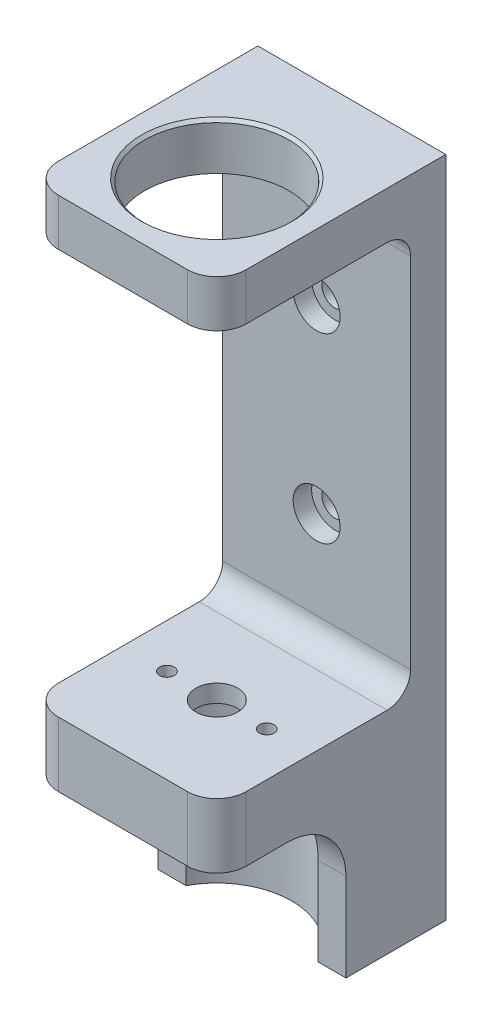
SolidWorks part; units mm, degrees
ref_plane "Alzado" through (0, 0, 0) normal (0, 0, 1) x (1, 0, 0)
ref_plane "Planta" through (0, 0, 0) normal (0, 1, 0) x (1, 0, 0)
ref_plane "Vista lateral" through (0, 0, 0) normal (1, 0, 0) x (0, 0, -1)
ref_plane "Plano1" through (14, 0, 0) normal (1, 0, 0) x (0, 0, -1)
sketch "Croquis1" plane through (14, 0, 0) normal (1, 0, 0) x (0, 0, -1)
  line L0 (-28, 72) -> (-28, 0)
  line L1 (-28, 0) -> (3, 0)
  line L2 (3, 0) -> (3, 72)
  line L3 (3, 72) -> (-28, 72)
extrude "Saliente-Extruir1" add sketch "Croquis1" against normal blind 28
sketch "Croquis2" plane through (-14, 0, 0) normal (-1, 0, 0) x (0, 0, 1)
  line L0 (28, 70) -> (1, 70)
  line L1 (1, 70) -> (1, 1)
  line L2 (1, 1) -> (28, 1)
  line L3 (28, 1) -> (28, 70)
extrude "Cortar-Extruir1" cut sketch "Croquis2" against normal through all
ref_plane "Plano2" through (0, 0, 14) normal (0, 0, -1) x (-1, 0, 0)
sketch "Croquis3" plane through (0, 0, 14) normal (0, 0, -1) x (-1, 0, 0)
  line L0 (-4.2, 72) -> (0, 72)
  line L1 (0, 72) -> (0, 73.5)
  line L2 (0, 73.5) -> (-2.7, 73.5)
  line L3 (0, 72) -> (0, 73.5) construction
  arc A0 (-2.7, 73.5) -> (-4.2, 72) centre (-4.2, 73.5) cw
ref_plane "Plano3" through (0, 0, 14) normal (0, 0, 1) x (1, 0, 0)
sketch "Croquis4" plane through (0, 0, 14) normal (0, 0, 1) x (1, 0, 0)
  line L0 (2.75, 2) -> (0, 2)
  line L1 (0, 2) -> (0, 1)
  line L2 (0, 1) -> (3.75, 1)
  line L3 (0, 2) -> (0, 1) construction
  arc A0 (3.75, 1) -> (2.75, 2) centre (3.75, 2) cw
sketch "Croquis5" plane through (0, 0, 14) normal (0, 0, -1) x (-1, 0, 0)
  line L0 (-13, -10) -> (0, -10)
  line L1 (0, -10) -> (0, 0)
  line L2 (0, 0) -> (-13, 0)
  line L3 (-13, 0) -> (-13, -10)
  line L4 (0, -10) -> (0, 0) construction
revolve "Revolución3" add sketch "Croquis5" angle 360 about L4 reverse direction yes
sketch "Croquis6" plane through (0, 0, 14) normal (0, 0, -1) x (-1, 0, 0)
  line L0 (-12.75, -10) -> (0, -10)
  line L1 (0, -10) -> (0, 2)
  line L2 (0, 2) -> (-2.3, 2)
  line L3 (-2.3, 2) -> (-2.3, 1)
  line L4 (-2.3, 1) -> (-2.25, 1)
  line L5 (-2.25, 1) -> (-2.25, 0)
  line L6 (-2.25, 0) -> (-12.75, 0)
  line L7 (-12.75, 0) -> (-12.75, -10)
  line L8 (0, -10) -> (0, 2) construction
revolve "Cortar-Revolución1" cut sketch "Croquis6" angle 360 about L8 reverse direction yes
hole_wizard "Diámetro de taladro Ø2.5 (2.5)2" positions "Croquis12" profile "Croquis11" hole size "Ø2.5" standard "Ansi Metric"
sketch "Croquis12" plane through (0, 1, 0) normal (0, 1, 0) x (1, 0, 0)
  point P0 (8.5, -14)
  point P1 (-8.5, -14)
sketch "Croquis11" plane through (8.5, 1, 14) normal (1, 0, 0) x (0, 0, 1)
  line L0 (0, 0) -> (0, 11)
  line L1 (0, 11) -> (1.25, 11)
  line L2 (1.25, 11) -> (1.25, 0)
  line L5 (1.25, 0) -> (0, 0)
  line L11 (0, -6.35) -> (0, 107.95) construction
  dimension "Diámetro de taladro hasta el siguiente" = 2.5
  dimension "Profundidad de taladro hasta el siguiente" = 11
fillet "Redondeo3" radius 5 2 edges at (0, 70, 1) (0, 1, 1) tangent propagation no
fillet "Redondeo4" radius 3 4 edges at (-14, 0.5, 28) (14, 71, 28) (14, 0.5, 28) (-14, 71, 28) tangent propagation no
sketch "Croquis14" plane through (0, 0, 0) normal (0, -1, 0) x (1, 0, 0)
  line L4 (11, 28) -> (-11, 28)
  line L5 (-14, 25) -> (-14, -3)
  line L6 (-14, -3) -> (14, -3)
  line L7 (14, -3) -> (14, 25)
  line L8 (11, 28) -> (-11, 28)
  line L9 (-14, 25) -> (-14, -3)
  line L10 (-14, -3) -> (14, -3)
  line L11 (14, -3) -> (14, 25)
  circle A0 centre (0, 14) radius 13 construction
  circle A1 centre (0, 14) radius 13
  arc A2 (-11, 28) -> (-14, 25) centre (-11, 25) ccw
  arc A3 (14, 25) -> (11, 28) centre (11, 25) ccw
  arc A4 (-11, 28) -> (-14, 25) centre (-11, 25) ccw
  arc A5 (14, 25) -> (11, 28) centre (11, 25) ccw
  dimension "D1" = 0
extrude "Saliente-Extruir2" add sketch "Croquis14" along normal blind 10
sketch "Croquis15" plane through (0, 0, -3) normal (0, 0, -1) x (-1, 0, 0)
  line L4 (-14, 72) -> (-14, -10)
  line L5 (-14, -10) -> (14, -10)
  line L6 (14, -10) -> (14, 72)
  line L7 (14, 72) -> (-14, 72)
  line L8 (-14, 72) -> (-14, -10)
  line L9 (-14, -10) -> (14, -10)
  line L10 (14, -10) -> (14, 72)
  line L11 (14, 72) -> (-14, 72)
  dimension "D1" = 0
extrude "Saliente-Extruir3" add sketch "Croquis15" along normal blind 6
sketch "Croquis16" plane through (0, 0, 0) normal (0, -1, 0) x (1, 0, 0)
  line L0 (0, 14) -> (2.7, 14) construction
  circle A0 centre (0, 14) radius 3.55
  dimension "D1" = 7.1
extrude "Cortar-Extruir2" cut sketch "Croquis16" against normal up to surface (72 mm away) up to face at (0, 72, 14.8738)
sketch "Croquis17" plane through (0, 72, 0) normal (0, 1, 0) x (1, 0, 0)
  line L4 (-11, -28) -> (11, -28)
  line L5 (14, -25) -> (14, 9)
  line L6 (14, 9) -> (-14, 9)
  line L7 (-14, 9) -> (-14, -25)
  line L8 (-11, -28) -> (11, -28)
  line L9 (14, -25) -> (14, 9)
  line L10 (14, 9) -> (-14, 9)
  line L11 (-14, 9) -> (-14, -25)
  circle A0 centre (0, -14) radius 3.55 construction
  circle A1 centre (0, -14) radius 3.55
  arc A2 (11, -28) -> (14, -25) centre (11, -25) ccw
  arc A3 (-14, -25) -> (-11, -28) centre (-11, -25) ccw
  arc A4 (11, -28) -> (14, -25) centre (11, -25) ccw
  arc A5 (-14, -25) -> (-11, -28) centre (-11, -25) ccw
  dimension "D1" = 0
extrude "Saliente-Extruir4" add sketch "Croquis17" along normal blind 6
sketch "Croquis18" plane through (-14, 0, 0) normal (-1, 0, 0) x (0, 0, 1)
  line L0 (6, 70) -> (1, 70)
  line L1 (-3, 66) -> (-3, 5)
  line L2 (1, 1) -> (6, 1)
  line L8 (25, 70) -> (25, 78)
  line L9 (25, 78) -> (-9, 78)
  line L10 (-9, 78) -> (-9, -10)
  line L11 (-9, -10) -> (25, -10)
  line L12 (25, -10) -> (25, 1)
  line L13 (25, 1) -> (6, 1)
  line L14 (1, 6) -> (1, 65)
  line L15 (6, 70) -> (25, 70)
  line L16 (25, 70) -> (25, 78)
  line L17 (25, 78) -> (-9, 78)
  line L18 (-9, 78) -> (-9, -10)
  line L19 (-9, -10) -> (25, -10)
  line L20 (25, -10) -> (25, 1)
  line L21 (25, 1) -> (6, 1)
  line L22 (1, 6) -> (1, 65)
  line L23 (6, 70) -> (25, 70)
  arc A0 (-3, 5) -> (1, 1) centre (1, 5) ccw
  arc A1 (1, 70) -> (-3, 66) centre (1, 66) ccw
  arc A2 (1, 6) -> (6, 1) centre (6, 6) ccw
  arc A3 (6, 70) -> (1, 65) centre (6, 65) ccw
  arc A4 (1, 6) -> (6, 1) centre (6, 6) ccw
  arc A5 (6, 70) -> (1, 65) centre (6, 65) ccw
  arc M18 (6, 1) -> (1, 6) centre (6, 6) cw
  line M19 (1, 6) -> (1, 65)
  arc M20 (1, 65) -> (6, 70) centre (6, 65) cw
  dimension "D2" = 4
  dimension "D3" = 4
  dimension "D1" = 0
extrude "Cortar-Extruir3" cut sketch "Croquis18" against normal through all contours L0 A1 L1 A0 L2 M18 M19 M20 region at (-14, 35.5, -0.8533)
sketch "Croquis19" plane through (0, -10, 0) normal (0, -1, 0) x (1, 0, 0)
  line L0 (-14, 8) -> (-11.25, 8)
  line L1 (11.25, 8) -> (14, 8)
  line L4 (11, 28) -> (-11, 28)
  line L5 (-14, 25) -> (-14, -9)
  line L6 (-14, -9) -> (14, -9)
  line L7 (14, -9) -> (14, 25)
  line L8 (11, 28) -> (-11, 28)
  line L9 (-14, 8) -> (-14, -9)
  line L10 (-14, -9) -> (14, -9)
  line L11 (14, -9) -> (14, 8)
  circle A0 centre (0, 14) radius 12.75 construction
  arc A1 (-11.25, 8) -> (11.25, 8) centre (0, 14) ccw
  arc A2 (14, 25) -> (11, 28) centre (11, 25) ccw
  arc A3 (-11, 28) -> (-14, 25) centre (-11, 25) ccw
  arc A4 (14, 25) -> (11, 28) centre (11, 25) ccw
  arc A5 (-11, 28) -> (-14, 25) centre (-11, 25) ccw
  circle M10 centre (0, 14) radius 12.75
  line M14 (-14, 25) -> (-14, -9)
  line M15 (-14, -9) -> (14, -9)
  line M16 (14, -9) -> (14, 25)
  dimension "D2" = 17
  dimension "D1" = 0
extrude "Saliente-Extruir5" add sketch "Croquis19" along normal blind 10 contours L1 L0 M10 M14 M15 M16 region at (0, -10, -2.185)
fillet "Redondeo5" radius 10 2 edges at (12.625, -10, 8) (-12.625, -10, 8)
sketch "Croquis20" plane through (0, 0, -3) normal (0, 0, 1) x (1, 0, 0)
  line L0 (0, 5) -> (0, 66) construction
  line L1 (14, 5) -> (-14, 5) construction
  line L2 (14, 66) -> (-14, 66) construction
  circle A0 centre (0, 51) radius 2.25
  circle A1 centre (0, 20) radius 2.25
  point P6 (0, 20)
  point P7 (0, 51)
  dimension "D3" = 4.5
  dimension "D4" = 4.5
  dimension "D1" = 15
  dimension "D2" = 15
extrude "Cortar-Extruir4" cut sketch "Croquis20" against normal through all
sketch "Croquis21" plane through (0, 0, -3) normal (0, 0, 1) x (1, 0, 0)
  line L4 (-14, 66) -> (-14, 5)
  line L5 (-14, 5) -> (14, 5)
  line L6 (14, 5) -> (14, 66)
  line L7 (14, 66) -> (-14, 66)
  line L8 (-14, 66) -> (-14, 5)
  line L9 (-14, 5) -> (14, 5)
  line L10 (14, 5) -> (14, 66)
  line L11 (14, 66) -> (-14, 66)
  circle A0 centre (0, 20) radius 2.25 construction
  circle A1 centre (0, 20) radius 2.25
  circle A2 centre (0, 51) radius 2.25 construction
  circle A3 centre (0, 51) radius 2.25
  circle A4 centre (0, 51) radius 4
  circle A5 centre (0, 20) radius 4
  circle M6 centre (0, 51) radius 2.25
  circle M7 centre (0, 20) radius 2.25
  dimension "D2" = 8
  dimension "D3" = 8
  dimension "D1" = 0
extrude "Cortar-Extruir5" cut sketch "Croquis21" against normal blind 3.15 contours A4 M6 | A5 M7 region at (-3.8869, 51, -3) region at (-3.8869, 20, -3)
sketch "Croquis22" plane through (0, 0, 0) normal (0, -1, 0) x (1, 0, 0)
  circle A0 centre (8.5, 14) radius 1.25 construction
  circle A1 centre (0, 14) radius 12.75
  circle A2 centre (0, 14) radius 12.75
  circle A3 centre (0, 14) radius 3.55 construction
  circle A4 centre (-8.5, 14) radius 1.25 construction
  circle A5 centre (8.5, 14) radius 1.25
  circle A6 centre (0, 14) radius 3.55
  circle A7 centre (-8.5, 14) radius 1.25
  dimension "D1" = 0
extrude "Saliente-Extruir6" add sketch "Croquis22" along normal blind 2
sketch "Croquis23" plane through (0, 78, 0) normal (0, 1, 0) x (1, 0, 0)
  line L0 (-16, 9) -> (-16, -25)
  line L1 (-11, -30) -> (11, -30)
  line L2 (16, -25) -> (16, 9)
  line L4 (-11, -28) -> (11, -28)
  line L5 (14, -25) -> (14, 9)
  line L6 (14, 9) -> (-14, 9)
  line L7 (-14, 9) -> (-14, -25)
  line L8 (-11, -28) -> (11, -28)
  line L9 (14, -25) -> (14, 9)
  line L10 (14, 9) -> (-14, 9)
  line L11 (-14, 9) -> (-14, -25)
  line L12 (14, 9) -> (16, 9)
  line L13 (-14, 9) -> (-16, 9)
  line L14 (16, -25) -> (16, 11) construction
  line L15 (16, 11) -> (-16, 11) construction
  line L16 (-16, 11) -> (-16, -25) construction
  arc A0 (-16, -25) -> (-11, -30) centre (-11, -25) ccw
  arc A1 (11, -30) -> (16, -25) centre (11, -25) ccw
  arc A2 (-14, -25) -> (-11, -28) centre (-11, -25) ccw
  arc A3 (11, -28) -> (14, -25) centre (11, -25) ccw
  arc A4 (-14, -25) -> (-11, -28) centre (-11, -25) ccw
  arc A5 (11, -28) -> (14, -25) centre (11, -25) ccw
  arc M13 (-14, -25) -> (-11, -28) centre (-11, -25) ccw
  line M14 (-11, -28) -> (11, -28)
  arc M15 (11, -28) -> (14, -25) centre (11, -25) ccw
  line M16 (14, -25) -> (14, 9)
  line M18 (-14, 9) -> (-14, -25)
  dimension "D1" = 0
  dimension "D2" = 2
extrude "Saliente-Extruir7" add sketch "Croquis23" against normal up to surface (8 mm away) contours L1 A1 L2 L12 L13 L0 A0 M16 M15 M14 M13 M18 region at (-15, 78, -8.4955) up to face at (-3.55, 70, 14)
sketch "Croquis24" plane through (-14, 0, 0) normal (-1, 0, 0) x (0, 0, 1)
  line L7 (1, 70) -> (-9, 70)
  line L8 (-9, 70) -> (-9, -20)
  line L9 (-9, -20) -> (8, -20)
  line L10 (18, -10) -> (25, -10)
  line L11 (25, -10) -> (25, 1)
  line L12 (25, 1) -> (1, 1)
  line L13 (-3, 5) -> (-3, 66)
  line L14 (1, 70) -> (-9, 70)
  line L15 (-9, 70) -> (-9, -20)
  line L16 (-9, -20) -> (8, -20)
  line L17 (18, -10) -> (25, -10)
  line L18 (25, -10) -> (25, 1)
  line L19 (25, 1) -> (1, 1)
  line L20 (-3, 5) -> (-3, 66)
  arc A3 (18, -10) -> (8, -20) centre (18, -20) ccw
  arc A4 (-3, 5) -> (1, 1) centre (1, 5) ccw
  arc A5 (1, 70) -> (-3, 66) centre (1, 66) ccw
  arc A6 (18, -10) -> (8, -20) centre (18, -20) ccw
  arc A7 (-3, 5) -> (1, 1) centre (1, 5) ccw
  arc A8 (1, 70) -> (-3, 66) centre (1, 66) ccw
  dimension "D1" = 0
extrude "Saliente-Extruir8" add sketch "Croquis24" along normal blind 2
sketch "Croquis25" plane through (14, 0, 0) normal (1, 0, 0) x (0, 0, -1)
  line L7 (9, -20) -> (9, 70)
  line L8 (9, 70) -> (-1, 70)
  line L9 (3, 66) -> (3, 5)
  line L10 (-1, 1) -> (-25, 1)
  line L11 (-25, 1) -> (-25, -10)
  line L12 (-25, -10) -> (-18, -10)
  line L13 (-8, -20) -> (9, -20)
  line L14 (9, -20) -> (9, 70)
  line L15 (9, 70) -> (-1, 70)
  line L16 (3, 66) -> (3, 5)
  line L17 (-1, 1) -> (-25, 1)
  line L18 (-25, 1) -> (-25, -10)
  line L19 (-25, -10) -> (-18, -10)
  line L20 (-8, -20) -> (9, -20)
  arc A3 (3, 66) -> (-1, 70) centre (-1, 66) ccw
  arc A4 (-1, 1) -> (3, 5) centre (-1, 5) ccw
  arc A5 (-8, -20) -> (-18, -10) centre (-18, -20) ccw
  arc A6 (3, 66) -> (-1, 70) centre (-1, 66) ccw
  arc A7 (-1, 1) -> (3, 5) centre (-1, 5) ccw
  arc A8 (-8, -20) -> (-18, -10) centre (-18, -20) ccw
  dimension "D1" = 0
extrude "Saliente-Extruir9" add sketch "Croquis25" along normal blind 2
sketch "Croquis26" plane through (0, -10, 0) normal (0, -1, 0) x (1, 0, 0)
  line L4 (-16, 1) -> (16, 1)
  line L5 (16, 1) -> (16, 25)
  line L6 (11, 30) -> (-11, 30)
  line L7 (-16, 25) -> (-16, 1)
  line L10 (11, 30) -> (-11, 30)
  line L15 (12.1063, 18) -> (16, 18)
  line L16 (16, 18) -> (16, 25)
  line L17 (16, 25) -> (14, 25)
  line L18 (11, 28) -> (-11, 28)
  line L19 (-14, 25) -> (-16, 25)
  line L20 (-16, 25) -> (-16, 18)
  line L21 (-16, 18) -> (-12.1063, 18)
  line L22 (12.1063, 18) -> (16, 18)
  line L23 (16, 18) -> (16, 25)
  line L24 (16, 25) -> (14, 25)
  line L25 (11, 28) -> (-11, 28)
  line L26 (-14, 25) -> (-16, 25)
  line L27 (-16, 25) -> (-16, 18)
  line L28 (-16, 18) -> (-12.1063, 18)
  arc A2 (16, 25) -> (11, 30) centre (11, 25) ccw
  arc A3 (-11, 30) -> (-16, 25) centre (-11, 25) ccw
  arc A4 (16, 25) -> (11, 30) centre (11, 25) ccw
  arc A5 (-11, 30) -> (-16, 25) centre (-11, 25) ccw
  arc A7 (12.1063, 18) -> (-12.1063, 18) centre (0, 14) ccw
  arc A8 (14, 25) -> (11, 28) centre (11, 25) ccw
  arc A9 (-11, 28) -> (-14, 25) centre (-11, 25) ccw
  arc A10 (12.1063, 18) -> (-12.1063, 18) centre (0, 14) ccw
  arc A11 (14, 25) -> (11, 28) centre (11, 25) ccw
  arc A12 (-11, 28) -> (-14, 25) centre (-11, 25) ccw
  line M20 (16, 25) -> (14, 25)
  arc M21 (14, 25) -> (11, 28) centre (11, 25) ccw
  line M22 (11, 28) -> (-11, 28)
  arc M23 (-11, 28) -> (-14, 25) centre (-11, 25) ccw
  line M24 (-14, 25) -> (-16, 25)
  dimension "D1" = 0
  dimension "D2" = 0
extrude "Saliente-Extruir10" add sketch "Croquis26" against normal up to surface (11 mm away) contours L10 A5 A4 M24 M23 M22 M21 M20 region at (0, -10, 28.4909) up to face at (3.55, 1, 14)
sketch "Croquis27" plane through (0, 78, 0) normal (0, 1, 0) x (1, 0, 0)
  circle A0 centre (0, -14) radius 12.3
  dimension "D1" = 24.6
extrude "Cortar-Extruir6" cut sketch "Croquis27" against normal up to surface (8 mm away) up to face at (-3.55, 70, 14)
sketch "Croquis28" plane through (0, -20, 0) normal (0, -1, 0) x (1, 0, 0)
  line L5 (16, 8) -> (11.25, 8)
  line L6 (-11.25, 8) -> (-16, 8)
  line L7 (-16, 8) -> (-16, -9)
  line L8 (-16, -9) -> (16, -9)
  line L9 (16, -9) -> (16, 8)
  line L10 (16, 8) -> (11.25, 8)
  line L11 (-11.25, 8) -> (-16, 8)
  line L12 (-16, 8) -> (-16, -9)
  line L13 (-16, -9) -> (16, -9)
  line L14 (16, -9) -> (16, 8)
  arc A1 (-11.25, 8) -> (11.25, 8) centre (0, 14) ccw
  arc A2 (-11.25, 8) -> (11.25, 8) centre (0, 14) ccw
  dimension "D1" = 0
extrude "Saliente-Extruir11" add sketch "Croquis28" along normal blind 15
chamfer "Chaflán1" distance 0.5 angle 45 1 edges at (0, 78, 26.3)
